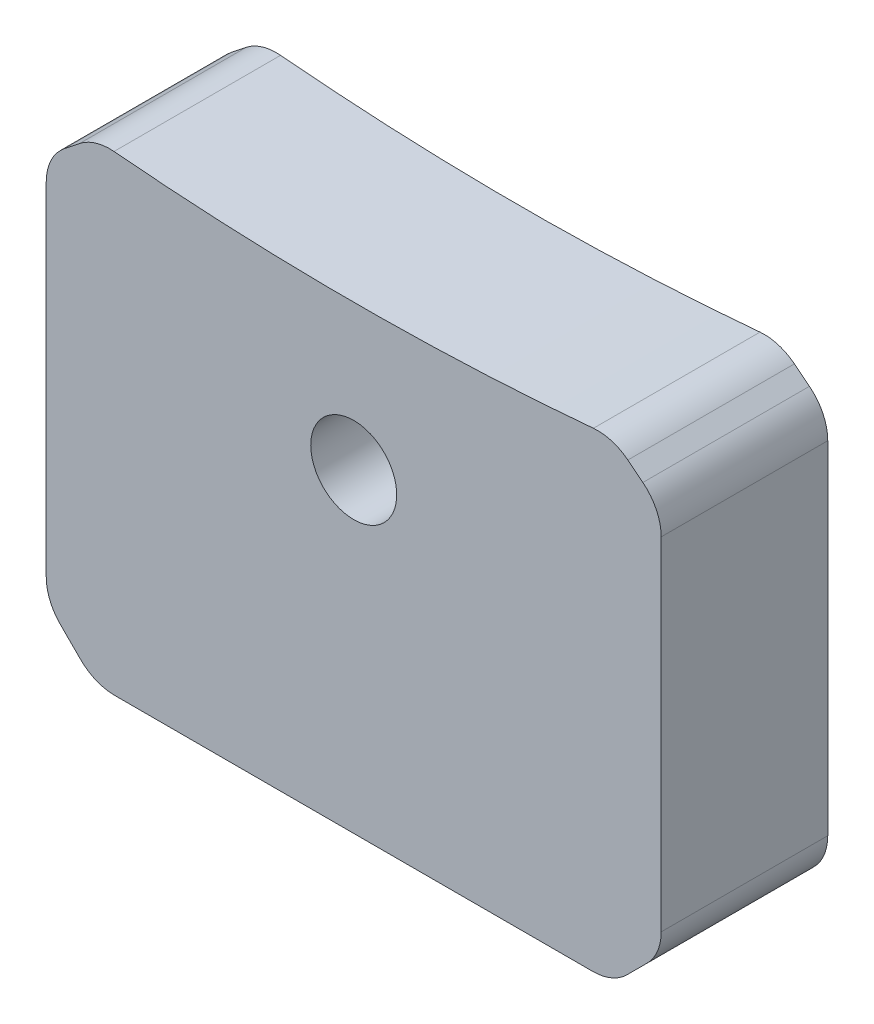
SolidWorks part; units mm, degrees
ref_plane "Front Plane" through (0, 0, 0) normal (0, 0, 1) x (1, 0, 0)
ref_plane "Top Plane" through (0, 0, 0) normal (0, 1, 0) x (1, 0, 0)
ref_plane "Right Plane" through (0, 0, 0) normal (1, 0, 0) x (0, 0, -1)
sketch "Sketch1" plane through (0, 0, 0) normal (0, 0, 1) x (1, 0, 0)
  line L1 (12.7, -16.15) -> (-12.7, -16.15)
  line L2 (12.7, -16.15) -> (12.7, 16.15)
  line L3 (12.7, 16.15) -> (-12.7, 16.15)
  line L4 (-12.7, -16.15) -> (-12.7, 16.15)
  line L5 (12.7, -16.15) -> (-12.7, 16.15) construction
  line L6 (12.7, 16.15) -> (-12.7, -16.15) construction
  point P0 (0, 0)
  dimension "D1" = 25.4
  dimension "D2" = 32.3
extrude "Boss-Extrude1" add sketch "Sketch1" along normal blind 6.88
sketch "Sketch3" plane through (0, 0, 0) normal (0, 0, -1) x (-1, 0, 0)
  line L0 (12.7, -16.15) -> (-12.7, -16.15) construction
  circle A0 centre (0, 0.4) radius 1.775 construction
  circle A1 centre (0, -3.15) radius 1.775 construction
  circle A2 centre (0, 113.85) radius 110 construction
  circle A3 centre (0, 113.85) radius 111
  circle A4 centre (0, -3.15) radius 1.775
  dimension "D2" = 3.55
  dimension "D1" = 16.55
extrude "Cut-Extrude1" cut sketch "Sketch3" against normal blind 6.88
chamfer "Chamfer1" distance 2 angle 45 4 edges at (12.7, 3.5789, 3.44) (12.7, -16.15, 3.44) (-12.7, 3.5789, 3.44) (-12.7, -16.15, 3.44)
fillet "Fillet1" radius 2 8 edges at (12.7, -14.15, 3.44) (10.7, -16.15, 3.44) (-12.7, 1.7736, 3.44) (-10.6928, 3.3662, 3.44) (10.6928, 3.3662, 3.44) (12.7, 1.7736, 3.44) (-10.7, -16.15, 3.44) (-12.7, -14.15, 3.44)
